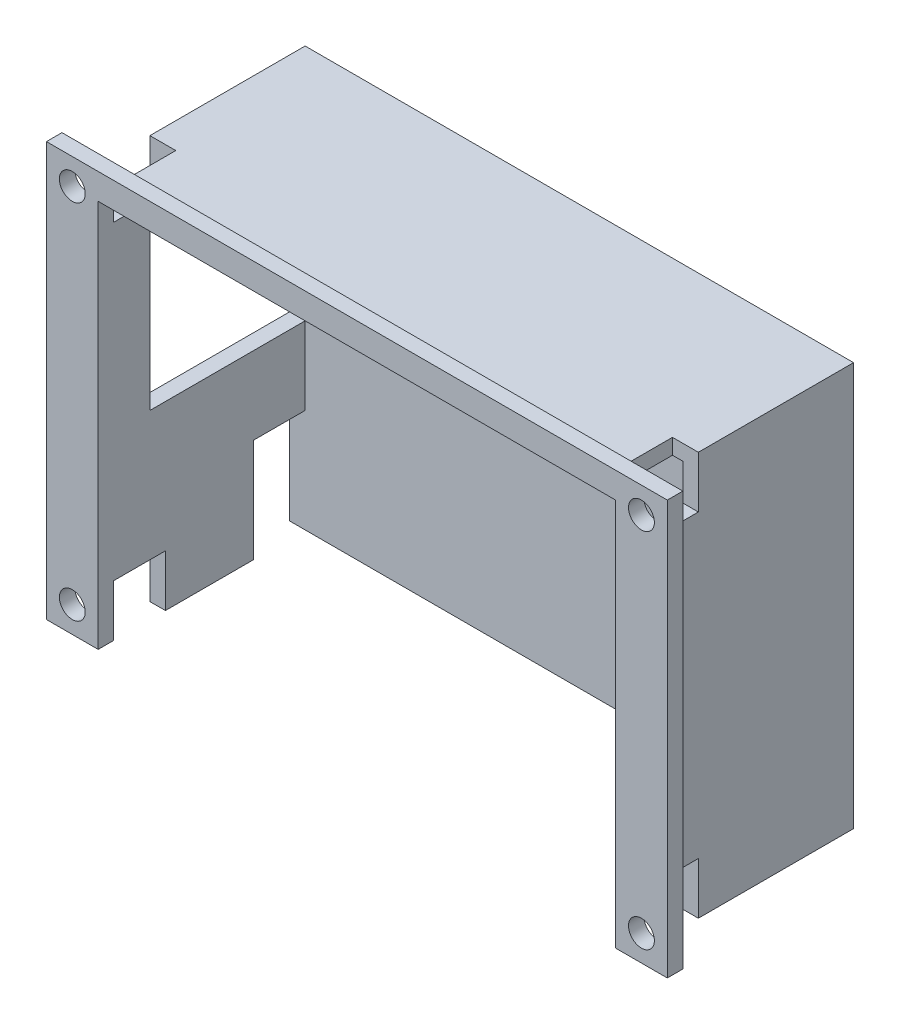
SolidWorks part; units mm, degrees
ref_plane "Front Plane" through (0, 0, 0) normal (0, 0, 1) x (1, 0, 0)
ref_plane "Top Plane" through (0, 0, 0) normal (0, 1, 0) x (1, 0, 0)
ref_plane "Right Plane" through (0, 0, 0) normal (1, 0, 0) x (0, 0, -1)
sketch "Sketch2" plane through (0, 0, 0) normal (0, 0, 1) x (1, 0, 0)
  line L1 (15.306, 62.8336) -> (75.306, 62.8336)
  line L2 (15.306, 62.8336) -> (15.306, 22.8336)
  line L3 (15.306, 22.8336) -> (75.306, 22.8336)
  line L4 (75.306, 62.8336) -> (75.306, 22.8336)
  circle A0 centre (17.806, 60.3336) radius 1.25
  circle A1 centre (17.806, 25.3336) radius 1.25
  circle A2 centre (72.806, 25.3336) radius 1.25
  circle A3 centre (72.806, 60.3336) radius 1.25
  dimension "D2" = 2.5
  dimension "D1" = 60
  dimension "D3" = 40
  dimension "D4" = 2.5
  dimension "D5" = 2.5
  dimension "D6" = 2.5
  dimension "D7" = 2.5
extrude "Boss-Extrude3" add sketch "Sketch2" along normal blind 1.5
sketch "Sketch3" plane through (0, 0, 0) normal (0, 0, -1) x (-1, 0, 0)
  line L0 (-75.306, 62.8336) -> (-15.306, 62.8336) construction
  line L1 (-71.806, 61.8336) -> (-18.806, 61.8336)
  line L2 (-71.806, 61.8336) -> (-71.806, 22.8336)
  line L3 (-71.806, 22.8336) -> (-18.806, 22.8336)
  line L4 (-18.806, 61.8336) -> (-18.806, 22.8336)
  line L6 (-15.306, 22.8336) -> (-75.306, 22.8336) construction
  line L7 (-75.306, 22.8336) -> (-75.306, 62.8336) construction
  line L8 (-15.306, 62.8336) -> (-15.306, 22.8336) construction
  dimension "D1" = 1
  dimension "D2" = 0
  dimension "D3" = 3.5
  dimension "D4" = 3.5
extrude "Boss-Extrude4" add sketch "Sketch3" along normal blind 20
sketch "Sketch7" plane through (0, 0, 1.5) normal (0, 0, 1) x (1, 0, 0)
  line L0 (75.306, 62.8336) -> (15.306, 62.8336) construction
  line L1 (20.306, 60.3336) -> (70.306, 60.3336)
  line L2 (20.306, 60.3336) -> (20.306, 22.8336)
  line L3 (20.306, 22.8336) -> (70.306, 22.8336)
  line L4 (70.306, 60.3336) -> (70.306, 22.8336)
  line L5 (15.306, 62.8336) -> (15.306, 22.8336) construction
  line L6 (75.306, 22.8336) -> (75.306, 62.8336) construction
  line L7 (15.306, 22.8336) -> (75.306, 22.8336) construction
  dimension "D1" = 2.5
  dimension "D2" = 5
  dimension "D3" = 5
  dimension "D4" = 0
extrude "Cut-Extrude4" cut sketch "Sketch7" against normal blind 20
sketch "Sketch8" plane through (71.806, 0, 0) normal (1, 0, 0) x (0, 0, -1)
  line L0 (20, 61.8336) -> (0, 61.8336) construction
  line L1 (0, 61.8336) -> (5, 61.8336)
  line L2 (0, 61.8336) -> (0, 56.8336)
  line L3 (0, 56.8336) -> (5, 56.8336)
  line L4 (5, 61.8336) -> (5, 56.8336)
  line L6 (0, 24.5836) -> (0, 22.8336) construction
  line L8 (0, 22.8336) -> (5, 22.8336)
  line L9 (0, 22.8336) -> (0, 27.8336)
  line L10 (0, 27.8336) -> (5, 27.8336)
  line L11 (5, 22.8336) -> (5, 27.8336)
  dimension "D1" = 5
  dimension "D2" = 5
extrude "Cut-Extrude5" cut sketch "Sketch8" against normal blind 2.5
sketch "Sketch11" plane through (18.806, 0, 0) normal (-1, 0, 0) x (0, 0, 1)
  line L1 (0, 62.8336) -> (-5, 62.8336)
  line L2 (0, 62.8336) -> (0, 57.8336)
  line L3 (0, 57.8336) -> (-5, 57.8336)
  line L4 (-5, 62.8336) -> (-5, 57.8336)
  line L5 (0, 22.8336) -> (-5, 22.8336)
  line L6 (0, 22.8336) -> (0, 27.8336)
  line L7 (0, 27.8336) -> (-5, 27.8336)
  line L8 (-5, 22.8336) -> (-5, 27.8336)
  dimension "D1" = 5
  dimension "D2" = 5
extrude "Cut-Extrude8" cut sketch "Sketch11" against normal blind 2.5
sketch "Sketch17" plane through (18.806, 0, 0) normal (-1, 0, 0) x (0, 0, 1)
  line L0 (-20, 22.8336) -> (-20, 61.8336) construction
  line L1 (-18.5, 40.3336) -> (-3.5, 40.3336)
  line L2 (-18.5, 40.3336) -> (-18.5, 57.8336)
  line L3 (-18.5, 57.8336) -> (-3.5, 57.8336)
  line L4 (-3.5, 40.3336) -> (-3.5, 57.8336)
  line L5 (-20, 22.8336) -> (-5, 22.8336) construction
  line L6 (1.5, 62.8336) -> (0, 62.8336) construction
  line L7 (-18.5, 22.8336) -> (-13.5, 22.8336)
  line L8 (-18.5, 22.8336) -> (-18.5, 32.8336)
  line L9 (-18.5, 32.8336) -> (-13.5, 32.8336)
  line L10 (-13.5, 22.8336) -> (-13.5, 32.8336)
  dimension "D1" = 5
  dimension "D2" = 17.5
  dimension "D3" = 15
  dimension "D4" = 1.5
  dimension "D5" = 10
  dimension "D6" = 1.5
  dimension "D7" = 5
extrude "Cut-Extrude13" cut sketch "Sketch17" against normal blind 2.5
